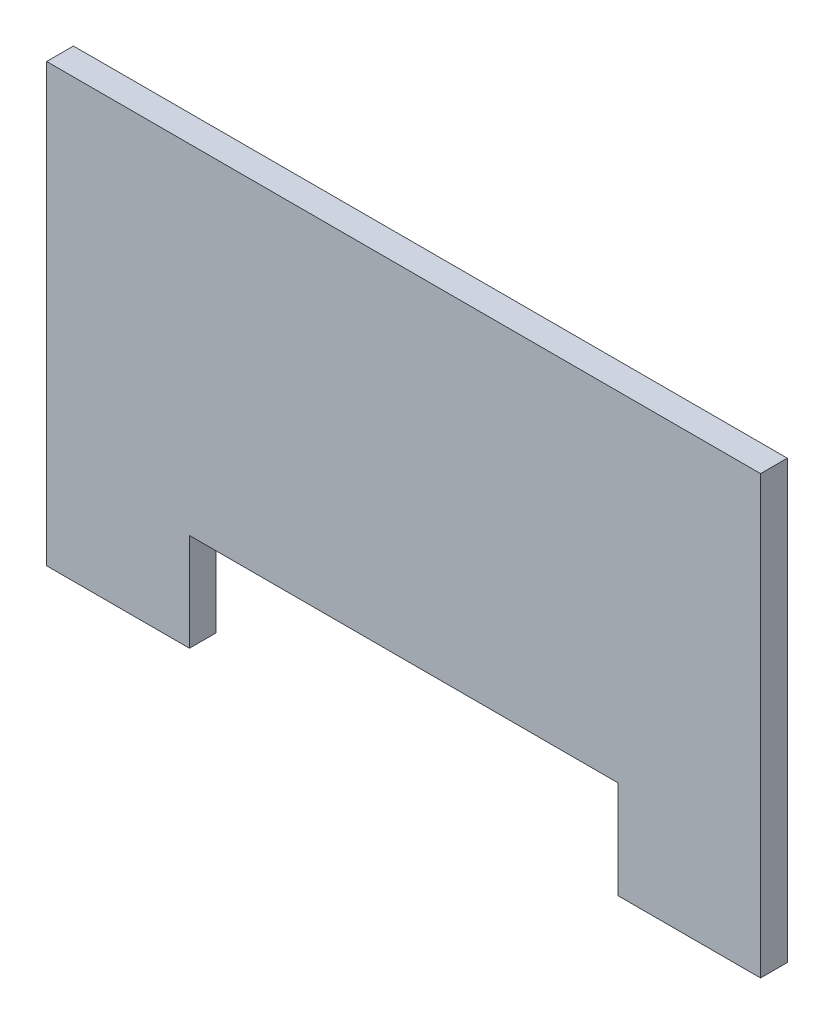
SolidWorks part; units mm, degrees
ref_plane "Front Plane" through (0, 0, 0) normal (0, 0, 1) x (1, 0, 0)
ref_plane "Top Plane" through (0, 0, 0) normal (0, 1, 0) x (1, 0, 0)
ref_plane "Right Plane" through (0, 0, 0) normal (1, 0, 0) x (0, 0, -1)
sketch "Sketch1" plane through (0, 0, 0) normal (0, 0, 1) x (1, 0, 0)
  line L0 (80, 3.175) -> (0, 3.175) construction
  line L1 (0, 52.125) -> (80, 52.125)
  line L2 (0, 52.125) -> (0, 3.175)
  line L3 (0, 3.175) -> (80, 3.175) construction
  line L4 (80, 52.125) -> (80, 3.175)
  line L5 (80, 52.125) -> (0, 52.125) construction
  line L6 (0, 52.125) -> (0, 3.175) construction
  line L7 (80, 52.125) -> (80, 3.175) construction
  line L8 (3, 49.125) -> (77, 49.125) construction
  line L9 (77, 49.125) -> (77, 6.175) construction
  line L10 (3, 6.175) -> (77, 6.175) construction
  line L11 (3, 49.125) -> (3, 6.175) construction
  line L12 (77, 49.125) -> (3, 49.125) construction
  line L13 (0, 17.125) -> (80, 17.125) construction
  line L14 (0, 14.125) -> (80, 14.125) construction
  line L15 (0, 40.925) -> (80, 40.925) construction
  line L16 (0, 37.925) -> (80, 37.925) construction
  line L17 (0, 37.925) -> (80, 37.925) construction
  line L18 (0, 40.925) -> (80, 40.925) construction
  line L19 (0, 14.125) -> (80, 14.125) construction
  line L20 (80, 17.125) -> (0, 17.125) construction
  line L21 (16, 3.175) -> (16, 14.125)
  line L22 (16, 14.125) -> (64, 14.125)
  line L23 (64, 14.125) -> (64, 3.175)
  line L24 (16, 3.175) -> (16, 14.125) construction
  line L25 (64, 14.125) -> (64, 3.175) construction
  line L26 (16, 3.175) -> (0, 3.175)
  line L27 (64, 3.175) -> (80, 3.175)
  circle A0 centre (37.5, 29.175) radius 21 construction
  circle A1 centre (37.5, 29.175) radius 24 construction
  circle A2 centre (37.5, 29.175) radius 24 construction
  circle A3 centre (37.5, 29.175) radius 21 construction
sketch "Sketch2" plane through (0, 0, 0) normal (1, 0, 0) x (0, 0, -1)
  line L1 (0, 52.125) -> (3, 52.125)
  line L2 (0, 52.125) -> (0, 3.175)
  line L3 (0, 3.175) -> (3, 3.175)
  line L4 (3, 52.125) -> (3, 3.175)
extrude "Boss-Extrude1" add sketch "Sketch1" against normal up to vertex (3 mm away) up to point (0, 52.125, -3)
